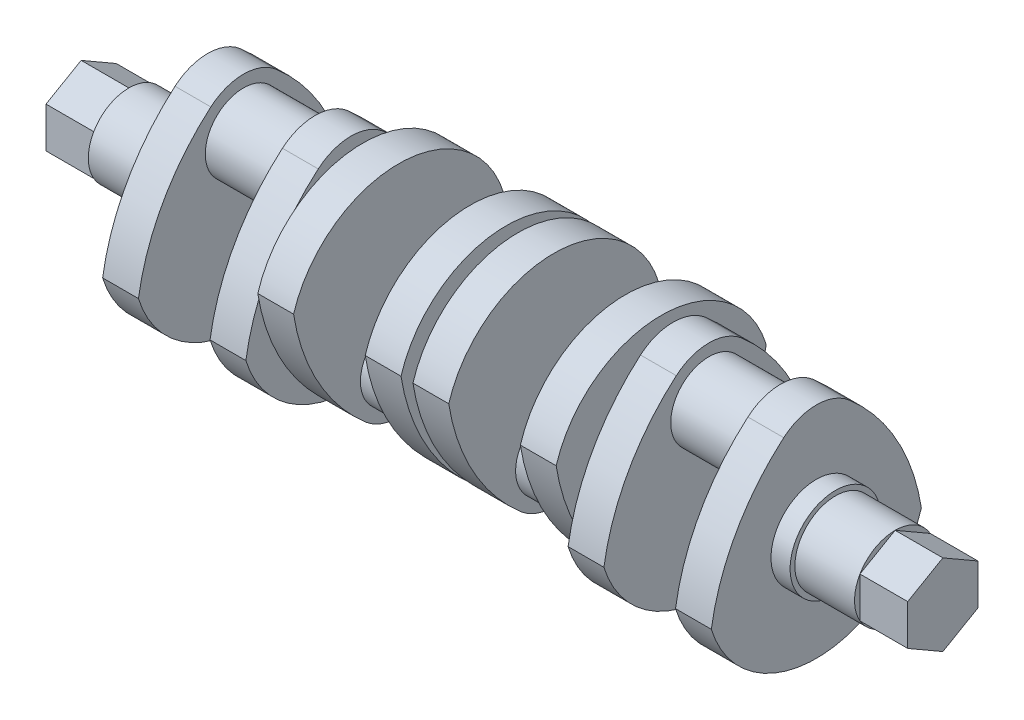
SolidWorks part; units mm, degrees
ref_plane "Front Plane" through (0, 0, 0) normal (0, 0, 1) x (1, 0, 0)
ref_plane "Top Plane" through (0, 0, 0) normal (0, 1, 0) x (1, 0, 0)
ref_plane "Right Plane" through (0, 0, 0) normal (1, 0, 0) x (0, 0, -1)
sketch "Sketch1" plane through (0, 0, 0) normal (1, 0, 0) x (0, 0, -1)
  circle A0 centre (0, 0) radius 17
  circle A1 centre (0, 0) radius 19
  dimension "D1" = 38
  dimension "D2" = 34
extrude "Boss-Extrude1" add sketch "Sketch1" along normal blind 25 contours A0
extrude "Boss-Extrude2" add sketch "Sketch1<3>" against normal blind 8 contours A1
sketch "Sketch1<3>" plane through (0, 0, 0) normal (1, 0, 0) x (0, 0, -1) same geometry as "Sketch1"
sketch "Sketch4" plane through (-8, 0, 0) normal (-1, 0, 0) x (0, 0, 1)
  arc A0 (-13.6681, 40.9431) -> (13.6681, 40.9431) centre (0, 25) cw
  arc A1 (-44, -13.4164) -> (44, -13.4164) centre (0, 0) ccw
  arc A2 (-44, -13.4164) -> (-13.6681, 40.9431) centre (44.9095, -27.3845) cw
  arc A3 (13.6681, 40.9431) -> (44, -13.4164) centre (-44.9095, -27.3845) cw
  dimension "D3" = 46
  dimension "D4" = 21
  dimension "D5" = 90
  dimension "D6" = 90
  dimension "D1" = 88
  dimension "D2" = 25
extrude "Boss-Extrude3" add sketch "Sketch4" along normal blind 15
sketch "Sketch5" plane through (-23, 0, 0) normal (-1, 0, 0) x (0, 0, 1)
  line L0 (0, 0) -> (0, 46) construction
  circle A1 centre (0, 25) radius 16
  arc A3 (13.6681, 40.9431) -> (-13.6681, 40.9431) centre (0, 25) ccw construction
  dimension "D1" = 32
extrude "Boss-Extrude4" add sketch "Sketch5" along normal blind 15
mirror "Mirror1" about plane through (-38, 25, 0) normal (-1, 0, 0) of "Boss-Extrude4", "Boss-Extrude3"
sketch "Sketch6" plane through (-68, 0, 0) normal (-1, 0, 0) x (0, 0, 1)
  circle A0 centre (0, 0) radius 17
  dimension "D1" = 34
extrude "Boss-Extrude5" add sketch "Sketch6" along normal blind 5
sketch "Sketch7" plane through (-73, 0, 0) normal (-1, 0, 0) x (0, 0, 1)
  circle A0 centre (0, 0) radius 17 construction
  arc A8 (-13.6681, -40.9431) -> (13.6681, -40.9431) centre (0, -25) ccw
  arc A9 (-44, 13.4164) -> (-13.6681, -40.9431) centre (44.9095, 27.3845) ccw
  arc A10 (44, 13.4164) -> (-44, 13.4164) centre (0, 0) ccw
  arc A11 (13.6681, -40.9431) -> (44, 13.4164) centre (-44.9095, 27.3845) ccw
  dimension "D1" = 21
  dimension "D2" = 90
  dimension "D3" = 46
  dimension "D4" = 13.6681
  dimension "D5" = 44
extrude "Boss-Extrude6" add sketch "Sketch7" along normal blind 15
sketch "Sketch8" plane through (-88, 0, 0) normal (-1, 0, 0) x (0, 0, 1)
  circle A0 centre (0, -25) radius 16
  dimension "D1" = 32
  dimension "D2" = 25
extrude "Boss-Extrude7" add sketch "Sketch8" along normal blind 30
sketch "Sketch9" plane through (-118, 0, 0) normal (-1, 0, 0) x (0, 0, 1)
  arc A4 (-13.6681, -40.9431) -> (13.6681, -40.9431) centre (0, -25) ccw
  arc A5 (13.6681, -40.9431) -> (44, 13.4164) centre (-44.9095, 27.3845) ccw
  arc A6 (44, 13.4164) -> (-44, 13.4164) centre (0, 0) ccw
  arc A7 (-44, 13.4164) -> (-13.6681, -40.9431) centre (44.9095, 27.3845) ccw
  arc A8 (-13.6681, -40.9431) -> (13.6681, -40.9431) centre (0, -25) ccw
  arc A9 (13.6681, -40.9431) -> (44, 13.4164) centre (-44.9095, 27.3845) ccw
  arc A10 (44, 13.4164) -> (-44, 13.4164) centre (0, 0) ccw
  arc A11 (-44, 13.4164) -> (-13.6681, -40.9431) centre (44.9095, 27.3845) ccw
  dimension "D1" = 0
extrude "Boss-Extrude8" add sketch "Sketch9" along normal blind 15
sketch "Sketch10" plane through (-133, 0, 0) normal (-1, 0, 0) x (0, 0, 1)
  circle A0 centre (0, 0) radius 17
  dimension "D1" = 34
extrude "Boss-Extrude9" add sketch "Sketch10" along normal blind 2.5
mirror "Mirror2" about plane through (-135.5, 0, 0) normal (-1, 0, 0) of bodies 110
sketch "Sketch11" plane through (25, 0, 0) normal (1, 0, 0) x (0, 0, -1)
  line L0 (0, 42.8357) -> (0, -34.1709) construction
  line L1 (14.7224, -8.5) -> (14.7224, 8.5)
  line L2 (14.7224, 8.5) -> (0, 17)
  line L3 (0, 17) -> (-14.7224, 8.5)
  line L4 (-14.7224, 8.5) -> (-14.7224, -8.5)
  line L5 (-14.7224, -8.5) -> (0, -17)
  line L6 (0, -17) -> (14.7224, -8.5)
  circle A0 centre (0, 0) radius 14.7224 construction
  point P11 (0, 0)
extrude "Boss-Extrude10" add sketch "Sketch11" along normal blind 20
sketch "Sketch12" plane through (-296, 0, 0) normal (-1, 0, 0) x (0, 0, 1)
  line L6 (-14.7224, -8.5) -> (0, -17)
  line L7 (-14.7224, 8.5) -> (-14.7224, -8.5)
  line L8 (0, 17) -> (-14.7224, 8.5)
  line L9 (14.7224, 8.5) -> (0, 17)
  line L10 (14.7224, -8.5) -> (14.7224, 8.5)
  line L11 (0, -17) -> (14.7224, -8.5)
  line L12 (-14.7224, -8.5) -> (0, -17)
  line L13 (-14.7224, 8.5) -> (-14.7224, -8.5)
  line L14 (0, 17) -> (-14.7224, 8.5)
  line L15 (14.7224, 8.5) -> (0, 17)
  line L16 (14.7224, -8.5) -> (14.7224, 8.5)
  line L17 (0, -17) -> (14.7224, -8.5)
  circle A1 centre (0, 0) radius 17
  circle A2 centre (0, 0) radius 17
  dimension "D1" = 0
  dimension "D2" = 0
extrude "Boss-Extrude11" add sketch "Sketch12" along normal blind 20 contours L12 L17 L16 L15 L14 L13 region at (-296, 0, 0)
